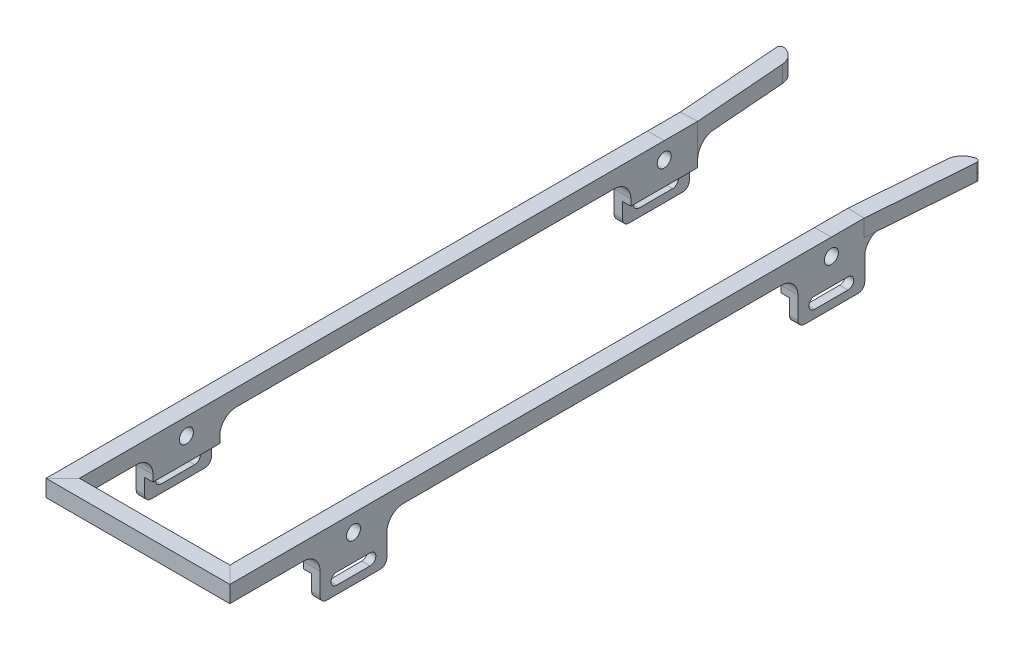
SolidWorks part; units mm, degrees
ref_plane "Front Plane" through (0, 0, 0) normal (0, 0, 1) x (1, 0, 0)
ref_plane "Top Plane" through (0, 0, 0) normal (0, 1, 0) x (1, 0, 0)
ref_plane "Right Plane" through (0, 0, 0) normal (1, 0, 0) x (0, 0, -1)
sketch "rail_path" plane through (0, 0, 0) normal (0, 1, 0) x (1, 0, 0)
  line L0 (28.575, 111.125) -> (28.575, 123.825)
  line L1 (-28.575, -111.125) -> (28.575, -111.125)
  line L2 (-28.575, -111.125) -> (-28.575, 111.125)
  line L3 (-28.575, 111.125) -> (28.575, 111.125) construction
  line L4 (28.575, -111.125) -> (28.575, 111.125)
  line L5 (-28.575, -111.125) -> (28.575, 111.125) construction
  line L6 (-28.575, 111.125) -> (28.575, -111.125) construction
  line L7 (-28.575, 111.125) -> (-28.575, 123.825)
  line L8 (28.575, 123.825) -> (31.75, 165.1)
  line L9 (-28.575, 123.825) -> (-31.75, 165.1)
  point P0 (0, 0)
  dimension "D1" = 222.25
  dimension "D2" = 57.15
  dimension "D3" = 12.7
  dimension "D4" = 12.7
  dimension "D5" = 41.275
  dimension "D6" = 3.175
  dimension "D7" = 3.175
sketch "rail_profile" plane through (0, 0, 0) normal (0, 0, 1) x (1, 0, 0)
  line L0 (-28.575, 0) -> (28.575, 0) construction
  line L1 (28.575, 0) -> (34.925, 0)
  line L2 (28.575, 0) -> (28.575, 6.35)
  line L3 (28.575, 6.35) -> (34.925, 6.35)
  line L4 (34.925, 0) -> (34.925, 6.35)
  line L5 (-28.575, 0) -> (28.575, 0) construction
  point P8 (0, 0)
  dimension "D1" = 6.35
  dimension "D2" = 6.35
sweep "Sweep1" add profiles "rail_profile" path "rail_path"
sketch "clip_profile" plane through (0, 0, 0) normal (0, 0, 1) x (1, 0, 0)
  line L4 (28.575, 0) -> (-28.575, 0)
  line L12 (-28.575, 6.35) -> (28.575, 6.35)
  line L34 (34.925, -17.272) -> (31.75, -17.272)
  line L38 (28.575, -8.89) -> (31.75, -8.89)
  line L39 (31.75, -17.272) -> (31.75, -8.89)
  line L47 (31.75, 6.35) -> (38.0813, 6.35)
  line L48 (34.925, -17.272) -> (34.925, -8.89)
  line L49 (38.0813, 6.35) -> (38.0813, 0)
  line L50 (28.575, -8.89) -> (34.925, -8.89)
  line L51 (28.575, -8.89) -> (28.575, 0)
  line L52 (28.575, 0) -> (34.925, 0)
  line L53 (34.925, -8.89) -> (34.925, 0)
  line L54 (31.75, 6.35) -> (38.0813, 6.35)
  line L55 (38.0813, 6.35) -> (38.0813, 0)
  line L56 (38.0813, 0) -> (31.75, 0)
  line L57 (31.75, 0) -> (28.575, 0)
  line L58 (38.0813, 0) -> (31.75, 0)
  line L59 (-28.575, 0) -> (-31.75, 0)
  line L60 (-31.75, 0) -> (-38.0813, 0)
  line L61 (-38.0813, 0) -> (-38.0813, 6.35)
  line L62 (-38.0813, 6.35) -> (-31.75, 6.35)
  line L63 (-31.75, 6.35) -> (-28.575, 6.35)
  line L64 (31.75, 0) -> (28.575, 0)
  line L65 (28.575, 6.35) -> (31.75, 6.35)
  line L66 (-28.575, 0) -> (-31.75, 0)
  line L67 (-31.75, 0) -> (-38.0813, 0)
  line L68 (-38.0813, 0) -> (-38.0813, 6.35)
  line L69 (-38.0813, 6.35) -> (-31.75, 6.35)
  line L70 (-31.75, 6.35) -> (-28.575, 6.35)
  line L71 (28.575, 6.35) -> (31.75, 6.35)
  dimension "D1" = 8.89
  dimension "D2" = 3.175
  dimension "D4" = 8.382
ref_plane "BackClipPlane" through (0, 0, 70.485) normal (0, 0, -1) x (-1, 0, 0)
ref_plane "FrontClipPlane" through (0, 0, -111.125) normal (0, 0, -1) x (-1, 0, 0)
sketch "BackClipProfile" plane through (0, 0, 70.485) normal (0, 0, -1) x (-1, 0, 0)
  line L24 (-34.925, -8.89) -> (-34.925, 0) construction
  line L25 (-34.925, -17.272) -> (-34.925, -8.89) construction
  line L26 (-34.925, -17.272) -> (-31.75, -17.272) construction
  line L27 (-31.75, -17.272) -> (-31.75, -8.89) construction
  line L28 (-28.575, -8.89) -> (-31.75, -8.89) construction
  line L29 (-28.575, -8.89) -> (-28.575, 0) construction
  line L30 (-34.925, -8.89) -> (-34.925, 0)
  line L31 (-34.925, -17.272) -> (-34.925, -8.89)
  line L32 (-34.925, -17.272) -> (-31.75, -17.272)
  line L33 (-31.75, -17.272) -> (-31.75, -8.89)
  line L34 (-28.575, -8.89) -> (-31.75, -8.89)
  line L35 (-28.575, -8.89) -> (-28.575, 0)
  line L36 (-28.575, 0) -> (-34.925, 0)
sketch "FrontClipProfile" plane through (0, 0, -111.125) normal (0, 0, -1) x (-1, 0, 0)
  line L24 (-31.75, -17.272) -> (-31.75, -8.89) construction
  line L25 (-34.925, -17.272) -> (-31.75, -17.272) construction
  line L26 (-34.925, -17.272) -> (-34.925, -8.89) construction
  line L27 (-34.925, -8.89) -> (-34.925, 0) construction
  line L28 (-28.575, -8.89) -> (-31.75, -8.89) construction
  line L29 (-28.575, -8.89) -> (-28.575, 0) construction
  line L30 (-31.75, -17.272) -> (-31.75, -8.89)
  line L31 (-34.925, -17.272) -> (-31.75, -17.272)
  line L32 (-34.925, -17.272) -> (-34.925, -8.89)
  line L33 (-34.925, -8.89) -> (-34.925, 0)
  line L34 (-28.575, -8.89) -> (-31.75, -8.89)
  line L35 (-28.575, -8.89) -> (-28.575, 0)
  line L36 (-28.575, 0) -> (-34.925, 0)
extrude "BackClip" add sketch "BackClipProfile" along normal mid plane 25.4
mirror "BackClipMirror" about plane through (0, 0, 0) normal (1, 0, 0) of "BackClip"
extrude "FrontClip" add sketch "FrontClipProfile" along normal mid plane 25.4
mirror "FrontClipMirror" about plane through (0, 0, 0) normal (1, 0, 0) of "FrontClip"
sketch "Sketch8" plane through (28.575, 0, 0) normal (-1, 0, 0) x (0, 0, 1)
  line L0 (70.485, 3.4925) -> (70.485, -3.4925) construction
  line L9 (111.125, 6.35) -> (-111.125, 6.35) construction
  line L17 (111.125, 6.35) -> (-111.125, 6.35) construction
  circle A2 centre (70.485, 0) radius 2.667
  dimension "D2" = 5.334
extrude "Cut-Extrude1" cut sketch "Sketch8" against normal through all both and the other way through all
ref_plane "Plane1" through (0, 0, -20.32) normal (0, 0, -1) x (-1, 0, 0)
sketch "Sketch10" plane through (31.75, 0, 0) normal (-1, 0, 0) x (0, 0, 1)
  line L0 (64.135, -12.065) -> (76.835, -12.065) construction
  line L1 (64.135, -9.906) -> (76.835, -9.906)
  line L2 (64.135, -14.224) -> (76.835, -14.224)
  line L3 (57.785, -8.89) -> (83.185, -8.89) construction
  line L4 (70.485, 3.4925) -> (70.485, -3.4925) construction
  arc A0 (64.135, -9.906) -> (64.135, -14.224) centre (64.135, -12.065) ccw
  arc A1 (76.835, -14.224) -> (76.835, -9.906) centre (76.835, -12.065) ccw
  point P2 (70.485, -12.065)
  dimension "D2" = 2.159
  dimension "D1" = 3.175
  dimension "D3" = 12.7
fillet "Fillet1" radius 2.54 8 edges at (-33.3375, -17.272, -123.825) (-33.3375, -17.272, -98.425) (-33.3375, -17.272, 57.785) (-33.3375, -17.272, 83.185) (33.3375, -17.272, 57.785) (33.3375, -17.272, 83.185) (33.3375, -17.272, -98.425) (33.3375, -17.272, -123.825)
mirror "Mirror2" about plane through (0, 0, -20.32) normal (0, 0, -1) of "Cut-Extrude1"
extrude "Cut-Extrude3" cut sketch "Sketch10" against normal through all both and the other way through all
mirror "Mirror3" about plane through (0, 0, -20.32) normal (0, 0, -1) of "Cut-Extrude3"
fillet "Fillet3" radius 6.35 2 edges at (31.75, 3.175, -165.1) (-31.75, 3.175, -165.1)
fillet "Fillet5" radius 1.27 2 edges at (38.0813, 3.175, -164.613) (-38.0813, 3.175, -164.613)
fillet "Fillet10" radius 6.35 8 edges at (-31.75, 0, 57.785) (-31.75, 0, 83.185) (31.75, 0, 83.185) (31.75, 0, 57.785) (31.75, 0, -98.425) (-31.75, 0, -98.425) (31.75, 0, -123.825) (-31.75, 0, -123.825)
equation "\"rail_horizontal_clearance\"= 0.25 / 2"
